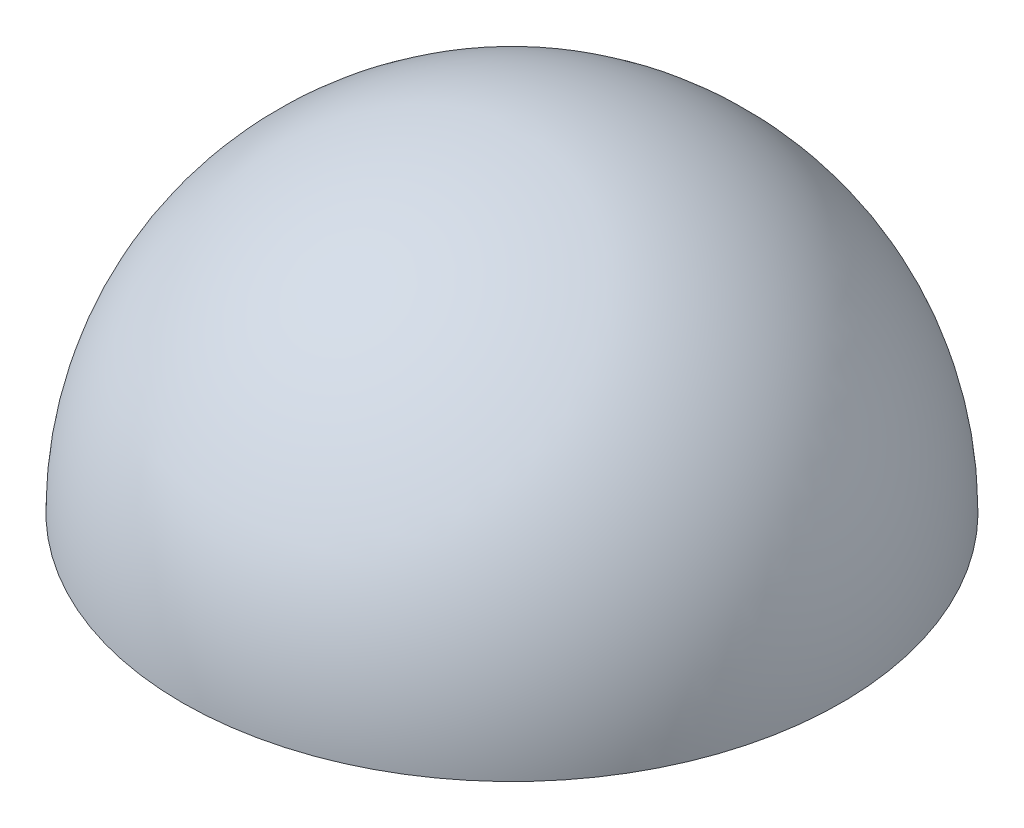
SolidWorks part; units mm, degrees
ref_plane "Front Plane" through (0, 0, 0) normal (0, 0, 1) x (1, 0, 0)
ref_plane "Top Plane" through (0, 0, 0) normal (0, 1, 0) x (1, 0, 0)
ref_plane "Right Plane" through (0, 0, 0) normal (1, 0, 0) x (0, 0, -1)
ref_plane "Plane1" through (0, 76.75, 0) normal (0, -1, 0) x (-1, 0, 0)
sketch "Sketch1" plane through (0, 76.75, 0) normal (0, -1, 0) x (-1, 0, 0)
  line L0 (38.5, 10) -> (-38.5, 10) construction
  line L1 (-13.5, -0.25) -> (7, -0.25)
  arc A0 (-13.5, -0.25) -> (7, -0.25) centre (-3.25, -0.25) ccw
  arc A1 (-13.75, 0) -> (7.25, 0) centre (-3.25, 0) ccw construction
  arc A2 (-13.75, 0) -> (7.25, 0) centre (-3.25, 0) ccw construction
  arc A3 (-13.5, -0.25) -> (7, -0.25) centre (-3.25, -0.25) cw construction
  point P7 (-3.25, -10.5)
  dimension "D1" = 20.5
revolve "Revolve1" add sketch "Sketch1" angle 180 about L1
sketch "Sketch2" plane through (0, 76.75, 0) normal (0, -1, 0) x (1, 0, 0)
  circle A2 centre (3.25, 0.25) radius 10.25 construction
  circle A3 centre (3.25, 0.25) radius 10.25 construction
  circle A4 centre (3.25, 0.25) radius 0.875
  dimension "D1" = 1.75
extrude "Cut-Extrude1" cut sketch "Sketch2" against normal blind 6
